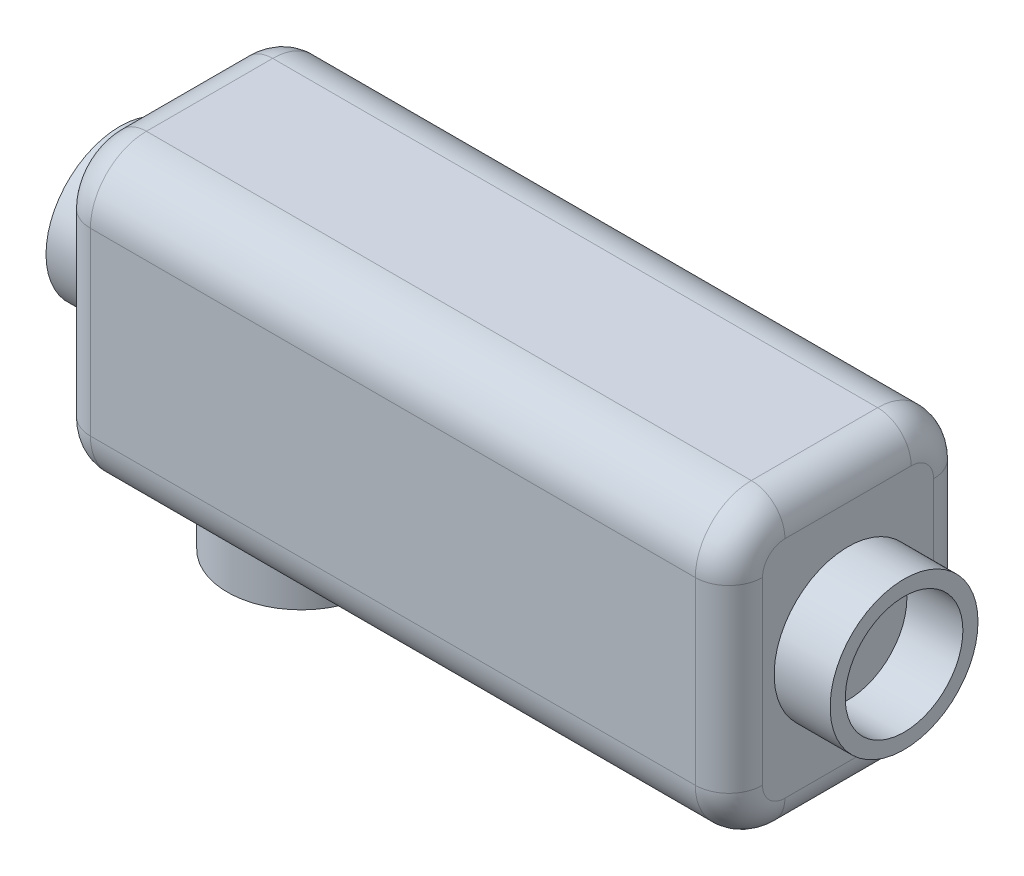
SolidWorks part; units mm, degrees
ref_plane "Front Plane" through (0, 0, 0) normal (0, 0, 1) x (1, 0, 0)
ref_plane "Top Plane" through (0, 0, 0) normal (0, 1, 0) x (1, 0, 0)
ref_plane "Right Plane" through (0, 0, 0) normal (1, 0, 0) x (0, 0, -1)
sketch "Sketch1" plane through (0, 0, 0) normal (1, 0, 0) x (0, 0, -1)
  circle A0 centre (0, 0) radius 13.335
  circle A1 centre (0, 0) radius 16.764
extrude "Boss-Extrude1" add sketch "Sketch1" along normal blind 12.7
sketch "Sketch2" plane through (0, 0, 0) normal (-1, 0, 0) x (0, 0, 1)
  line L1 (-27.0144, -33.0964) -> (27.0144, -33.0964)
  line L2 (-27.0144, -33.0964) -> (-27.0144, 33.0964)
  line L3 (-27.0144, 33.0964) -> (27.0144, 33.0964)
  line L4 (27.0144, -33.0964) -> (27.0144, 33.0964)
  line L5 (-27.0144, -33.0964) -> (27.0144, 33.0964) construction
  line L6 (-27.0144, 33.0964) -> (27.0144, -33.0964) construction
  point P0 (0, 0)
extrude "Boss-Extrude2" add sketch "Sketch2" along normal blind 152.4
fillet "Fillet1" radius 7.62 4 edges at (0, 0, 27.0144) (0, -33.0964, 0) (0, 0, -27.0144) (0, 33.0964, 0)
fillet "Fillet2" radius 12.7 6 edges at (-2.2318, 30.8646, -24.7825) (-2.2318, 30.8646, 24.7825) (-2.2318, -30.8646, -24.7825) (-80.01, -33.0964, -27.0144) (-80.01, 33.0964, 27.0144) (-80.01, 33.0964, -27.0144)
fillet "Fillet3" radius 12.7 2 edges at (-2.2318, -30.8646, 24.7825) (-80.01, -33.0964, 27.0144)
fillet "Fillet4" radius 7.62 8 edges at (-152.4, 29.3767, -23.2946) (-152.4, 33.0964, 0) (-152.4, 29.3767, 23.2946) (-152.4, 0, 27.0144) (-152.4, -29.3767, 23.2946) (-152.4, -33.0964, 0) (-152.4, -29.3767, -23.2946) (-152.4, 0, -27.0144)
sketch "Sketch3" plane through (-152.4, 0, 0) normal (-1, 0, 0) x (0, 0, 1)
  circle A0 centre (0, 0) radius 13.335
  circle A1 centre (0, 0) radius 16.764
extrude "Boss-Extrude3" add sketch "Sketch3" along normal blind 12.7
sketch "Sketch4" plane through (0, -33.0964, 0) normal (0, -1, 0) x (1, 0, 0)
  circle A0 centre (-123.9864, 0) radius 13.335
  circle A1 centre (-123.9864, 0) radius 16.764
extrude "Boss-Extrude4" add sketch "Sketch4" along normal blind 12.7
sketch "Sketch5" plane through (0, 0, -27.0144) normal (0, 0, -1) x (-1, 0, 0)
  line L0 (53.9967, 0) -> (87.8357, 0)
  line L1 (87.8357, 0) -> (87.8357, 6.35)
  line L2 (87.8357, 6.35) -> (96.4842, -3.175)
  line L3 (96.4842, -3.175) -> (87.8357, -12.7)
  line L4 (87.8357, -12.7) -> (87.8357, -6.35)
  line L5 (87.8357, -6.35) -> (53.9967, -6.35)
  line L6 (53.9967, -6.35) -> (53.9967, 0)
  point P3 (53.9967, -3.175)
  dimension "D1" = 6.35
  dimension "D2" = 6.35
  dimension "D3" = 6.35
extrude "Boss-Extrude5" add sketch "Sketch5" along normal blind 2.54
